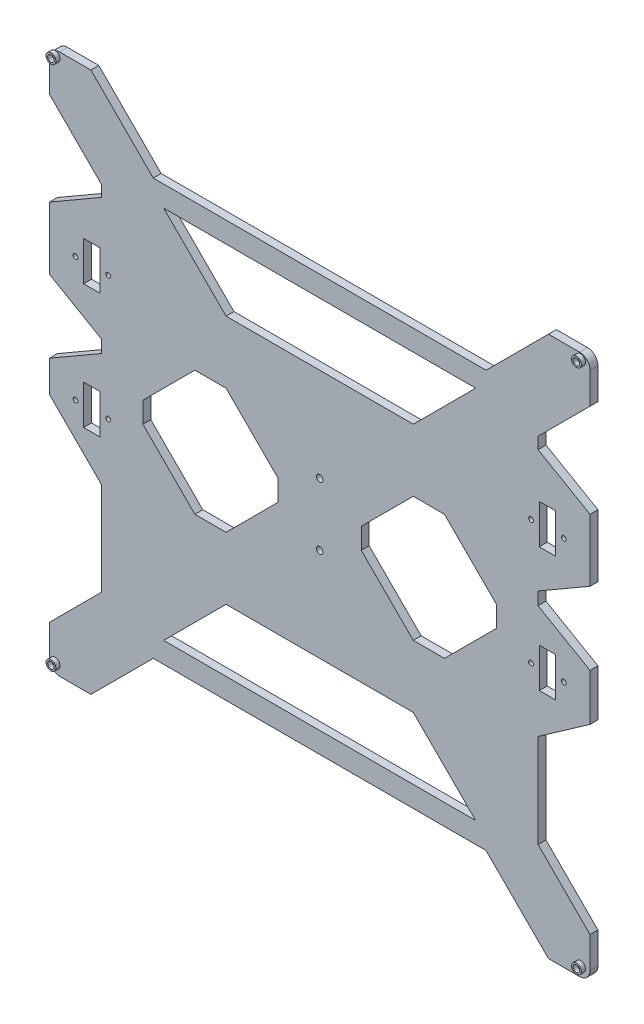
SolidWorks part; units mm, degrees
material "5052-H32"
ref_plane "Front Plane" through (0, 0, 0) normal (0, 0, 1) x (1, 0, 0)
ref_plane "Top Plane" through (0, 0, 0) normal (0, 1, 0) x (1, 0, 0)
ref_plane "Right Plane" through (0, 0, 0) normal (1, 0, 0) x (0, 0, -1)
sketch "Model" plane through (0, 0, 0) normal (0, 0, 1) x (1, 0, 0)
  line L0 (38.5361, 132.6139) -> (38.5361, 132.4727)
  line L1 (38.5361, -178.6774) -> (38.5361, -178.7219)
  line L2 (-253.5639, -197.5861) -> (-253.5639, -197.7273)
  line L3 (-290.6813, -31.2683) -> (-258.9313, -12.9374)
  line L4 (-258.9313, -82.0683) -> (-258.9313, -139.2183)
  line L5 (38.5361, 132.6139) -> (38.5361, 132.4727)
  line L6 (38.5361, -178.6774) -> (38.5361, -178.7219)
  line L7 (7.7687, -139.2183) -> (7.7687, -82.0683)
  line L8 (39.5187, -59.8367) -> (39.5187, -31.2683)
  line L9 (-23.9813, 95.7317) -> (-227.1813, 95.7317)
  line L10 (-290.6813, 108.4317) -> (-258.9313, 76.6817)
  line L11 (-30.3313, -145.5683) -> (-68.4313, -107.4683)
  line L12 (-23.9813, -158.2683) -> (14.1187, -196.3683)
  line L13 (39.5187, 108.4317) -> (39.5187, 127.4817)
  line L14 (-227.1813, 95.7317) -> (-265.2813, 133.8317)
  line L15 (-220.8313, 83.0317) -> (-182.7313, 44.9317)
  line L16 (-274.6813, -45.4288) -> (-254.6813, -45.4288) construction
  line L17 (39.5187, -170.9683) -> (7.7687, -139.2183)
  line L18 (-265.2813, -196.3683) -> (-227.1813, -158.2683)
  line L19 (-182.7313, -107.4683) -> (-68.4313, -107.4683)
  line L20 (-264.6813, -45.4288) -> (-264.6813, -43.5832) construction
  line L21 (7.7687, 76.6817) -> (39.5187, 108.4317)
  line L22 (-23.9813, 95.7317) -> (14.1187, 133.8317)
  line L23 (-30.3313, 83.0317) -> (-68.4313, 44.9317)
  line L24 (39.5187, -31.2683) -> (7.7687, -12.9374)
  line L25 (-258.9313, -139.2183) -> (-290.6813, -170.9683)
  line L26 (-182.7313, 44.9317) -> (-68.4313, 44.9317)
  line L27 (-220.8313, -145.5683) -> (-182.7313, -107.4683)
  line L28 (-220.8313, -145.5683) -> (-30.3313, -145.5683)
  line L29 (-258.9313, -82.0683) -> (-290.6813, -50.3183)
  line L30 (-290.6813, -31.2683) -> (-290.6813, -50.3183)
  line L31 (-274.6813, -43.9683) -> (-274.6813, -31.2683) construction
  line L32 (-258.9313, -12.9374) -> (-258.9313, -5.1492)
  line L33 (-201.7813, -69.3683) -> (-233.5313, -37.6183)
  line L34 (-182.7313, -69.3683) -> (-201.7813, -69.3683)
  line L35 (7.7687, -12.9374) -> (7.7687, -5.1492)
  line L36 (7.7687, -5.1492) -> (39.5187, 13.1817)
  line L37 (-150.9813, -37.6183) -> (-182.7313, -69.3683)
  line L38 (39.5187, -59.8367) -> (10.4646, -80.1806)
  line L39 (10.4646, -80.1806) -> (7.7687, -82.0683)
  line L40 (-100.1813, -37.6183) -> (-100.1813, -24.9183)
  line L41 (-150.9813, -37.6183) -> (-150.9813, -24.9183)
  line L42 (-150.9813, -24.9183) -> (-182.7313, 6.8317)
  line L43 (-182.7313, 6.8317) -> (-201.7813, 6.8317)
  line L44 (-201.7813, 6.8317) -> (-233.5313, -24.9183)
  line L45 (-233.5313, -24.9183) -> (-233.5313, -37.6183)
  line L46 (-17.6313, -24.9183) -> (-17.6313, -37.6183)
  line L47 (-49.3813, 6.8317) -> (-17.6313, -24.9183)
  line L48 (-220.8313, 83.0317) -> (-30.3313, 83.0317)
  line L49 (-68.4313, 6.8317) -> (-49.3813, 6.8317)
  line L50 (-100.1813, -24.9183) -> (-68.4313, 6.8317)
  line L51 (-100.1813, -37.6183) -> (-68.4313, -69.3683)
  line L52 (-68.4313, -69.3683) -> (-49.3813, -69.3683)
  line L53 (-49.3813, -69.3683) -> (-17.6313, -37.6183)
  line L54 (39.5187, 13.1817) -> (39.5187, 51.2817)
  line L55 (39.5187, 51.2817) -> (7.7687, 69.6126)
  line L56 (7.7687, 69.6126) -> (7.7687, 76.6817)
  line L57 (-258.9313, -5.1492) -> (-290.6813, 13.1817)
  line L58 (-265.2813, -196.3683) -> (-284.3313, -196.3683)
  line L59 (-290.6813, -190.0183) -> (-290.6813, -170.9683)
  line L60 (-290.6813, 108.4317) -> (-290.6813, 127.4817)
  line L61 (-284.3313, 133.8317) -> (-265.2813, 133.8317)
  line L62 (14.1187, 133.8317) -> (33.1687, 133.8317)
  line L63 (-290.6813, 13.1817) -> (-290.6813, 51.2817)
  line L64 (39.5187, -170.9683) -> (39.5187, -190.0183)
  line L65 (33.1687, -196.3683) -> (14.1187, -196.3683)
  line L66 (-258.9313, 76.6817) -> (-258.9313, 69.6126)
  line L67 (-258.9313, 69.6126) -> (-290.6813, 51.2817)
  line L68 (-274.6813, 30.5682) -> (-254.6813, 30.5682) construction
  line L69 (-254.6813, 30.5682) -> (23.5187, 30.5682) construction
  line L70 (23.5187, 30.5682) -> (23.5187, -45.4288) construction
  line L71 (-227.1813, -158.2683) -> (-23.9813, -158.2683)
  line L72 (38.5361, -178.6774) -> (38.5361, -178.7219)
  line L73 (3.5187, 30.5682) -> (3.5187, -45.4288) construction
  line L74 (-227.1813, -158.2683) -> (-23.9813, -158.2683)
  line L75 (38.5361, -178.6774) -> (38.5361, -178.7219)
  line L76 (-274.6813, 30.5682) -> (-274.6813, -45.4288) construction
  line L77 (-125.5813, 95.7317) -> (-125.5813, -158.2683) construction
  line L78 (-290.6813, -31.2683) -> (39.5187, -31.2683) construction
  arc A0 (33.1687, -196.3683) -> (39.5187, -190.0183) centre (33.1687, -190.0183) ccw
  arc A1 (-290.6813, -190.0183) -> (-284.3313, -196.3683) centre (-284.3313, -190.0183) ccw
  arc A2 (-290.6813, 127.4817) -> (-284.3313, 133.8317) centre (-284.3313, 127.4817) cw
  arc A3 (33.1687, 133.8317) -> (39.5187, 127.4817) centre (33.1687, 127.4817) cw
  circle A4 centre (-287.1253, -190.6025) radius 1.4605
  circle A5 centre (33.7529, -190.6025) radius 1.4605
  circle A6 centre (33.7529, 130.2757) radius 1.4605
  circle A7 centre (-287.1253, 130.2757) radius 1.4605
  circle A8 centre (-274.6813, -45.4288) radius 1.4605
  circle A9 centre (-254.6813, -45.4288) radius 1.4605
  circle A10 centre (23.5187, -45.4288) radius 1.4605
  circle A11 centre (3.5187, -45.4288) radius 1.4605
  circle A12 centre (23.5187, 30.5682) radius 1.4605
  circle A13 centre (3.5187, 30.5682) radius 1.4605
  circle A14 centre (-254.6813, 30.5682) radius 1.4605
  circle A15 centre (-274.6813, 30.5682) radius 1.4605
  circle A16 centre (-125.5813, -12.2183) radius 2
  circle A17 centre (-125.5813, -50.3183) radius 2
  point P34 (-254.6813, 42.5697)
  point P35 (22.9067, 30.5682)
  point P72 (-125.5813, -31.2683)
  point P114 (-125.5813, 83.0317)
  point P120 (-233.5313, -31.2683)
  point P129 (-150.9813, -31.2683)
  point P149 (-125.5813, 44.9317)
  point P156 (-17.6313, -31.2683)
  dimension "D28" = 6.35
  dimension "D29" = 6.35
  dimension "D30" = 6.35
  dimension "D31" = 6.35
  dimension "D35" = 2.921
  dimension "D36" = 2.921
  dimension "D37" = 2.921
  dimension "D38" = 2.921
  dimension "D53" = 2.921
  dimension "D54" = 2.921
  dimension "D56" = 4
  dimension "D57" = 4
  dimension "D1" = 330.2
  dimension "D2" = 330.2
  dimension "D3" = 135
  dimension "D4" = 135
  dimension "D5" = 38.1
  dimension "D6" = 135
  dimension "D7" = 120
  dimension "D8" = 19.05
  dimension "D9" = 135
  dimension "D10" = 19.05
  dimension "D11" = 31.75
  dimension "D12" = 190.5
  dimension "D13" = 114.3
  dimension "D14" = 38.1
  dimension "D15" = 114.3
  dimension "D16" = 135
  dimension "D17" = 6.35
  dimension "D18" = 38.1
  dimension "D19" = 135
  dimension "D20" = 135
  dimension "D21" = 6.35
  dimension "D22" = 19.05
  dimension "D23" = 25.4
  dimension "D24" = 50.8
  dimension "D25" = 120
  dimension "D26" = 135
  dimension "D27" = 127
  dimension "D32" = 19.05
  dimension "D33" = 19.05
  dimension "D34" = 19.05
  dimension "D39" = 120
  dimension "D40" = 19.05
  dimension "D41" = 120
  dimension "D42" = 120
  dimension "D43" = 50.8
  dimension "D44" = 19.05
  dimension "D45" = 31.75
  dimension "D46" = 125
  dimension "D47" = 320.8782
  dimension "D48" = 320.8782
  dimension "D49" = 3.556
  dimension "D50" = 3.556
  dimension "D51" = 20
  dimension "D52" = 26
  dimension "D55" = 12.7
  dimension "D58" = 38.1
  dimension "D59" = 19.05
  dimension "D60" = 82.55
  dimension "D61" = 38.1
  dimension "D63" = 120
  dimension "D64" = 38.1
  dimension "D65" = 82.55
  dimension "D67" = 75.997
extrude "Boss-Extrude1" add sketch "Model" along normal mid plane 4.826 contours A3 L62 L22 L9 L14 L61 A2 L60 L10 L30 L29 L4 L25 L59 A1 L58 L18 L71 L12 L65 A0 L64 L17 L7 L39 L38 L8 L21 L13 A17 A16 A14 A13 A12 A10 A9 region at (-125.199, -28.2686, 0)
sketch "Sketch1" plane through (0, 0, 2.413) normal (0, 0, 1) x (1, 0, 0)
  line L0 (23.5187, 30.5682) -> (23.5187, 17.7506) construction
  line L1 (-269.6813, -33.4288) -> (-259.6813, -33.4288)
  line L2 (-269.6813, -33.4288) -> (-269.6813, -57.4288)
  line L3 (-269.6813, -57.4288) -> (-259.6813, -57.4288)
  line L4 (-259.6813, -33.4288) -> (-259.6813, -57.4288)
  line L5 (-269.6813, 42.5712) -> (-259.6813, 42.5712)
  line L6 (-269.6813, 42.5712) -> (-269.6813, 18.5712)
  line L7 (-269.6813, 18.5712) -> (-259.6813, 18.5712)
  line L8 (-259.6813, 42.5712) -> (-259.6813, 18.5712)
  line L9 (8.5187, 42.5712) -> (18.5187, 42.5712)
  line L10 (8.5187, 42.5712) -> (8.5187, 18.5712)
  line L11 (8.5187, 18.5712) -> (18.5187, 18.5712)
  line L12 (18.5187, 42.5712) -> (18.5187, 18.5712)
  line L13 (8.5187, -33.4288) -> (18.5187, -33.4288)
  line L14 (8.5187, -33.4288) -> (8.5187, -57.4288)
  line L15 (8.5187, -57.4288) -> (18.5187, -57.4288)
  line L16 (18.5187, -33.4288) -> (18.5187, -57.4288)
  circle A1 centre (-274.6813, -45.4288) radius 1.4605 construction
  circle A5 centre (-274.6813, 30.5682) radius 1.4605 construction
  circle A8 centre (23.5187, 30.5682) radius 1.4605 construction
  circle A9 centre (23.5187, -45.4288) radius 1.4605 construction
  point P20 (13.5187, 42.5712)
  dimension "D3" = 12
  dimension "D4" = 5
  dimension "D5" = 10
  dimension "D8" = 100
  dimension "D11" = 100
  dimension "D15" = 12
  dimension "D1" = 10
  dimension "D2" = 24
  dimension "D6" = 24
  dimension "D7" = 5
  dimension "D9" = 24
  dimension "D10" = 5
  dimension "D12" = 10
  dimension "D13" = 10
  dimension "D14" = 24
  dimension "D16" = 5
extrude "Cut-Extrude1" cut sketch "Sketch1" against normal blind 10
sketch "Sketch2" plane through (0, 0, 2.413) normal (0, 0, 1) x (1, 0, 0)
  circle A0 centre (33.7529, -190.6025) radius 3
  circle A1 centre (33.7529, -190.6025) radius 2
  circle A2 centre (-287.1253, -190.6025) radius 2
  circle A3 centre (-287.1253, -190.6025) radius 3
  circle A4 centre (-287.1253, 130.2757) radius 2
  circle A5 centre (-287.1253, 130.2757) radius 3
  circle A6 centre (33.7529, 130.2757) radius 2
  circle A7 centre (33.7529, 130.2757) radius 3
  dimension "D1" = 6
  dimension "D2" = 4
extrude "Boss-Extrude2" add sketch "Sketch2" along normal blind 2.54
